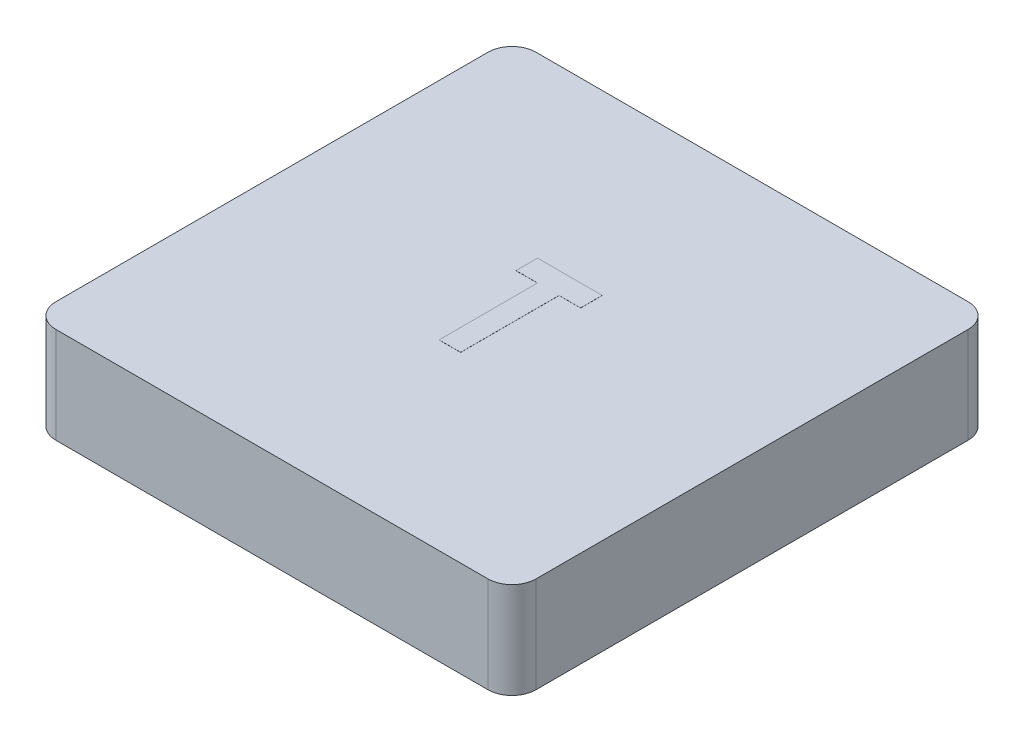
SolidWorks part; units mm, degrees
ref_plane "Front Plane" through (0, 0, 0) normal (0, 0, 1) x (1, 0, 0)
ref_plane "Top Plane" through (0, 0, 0) normal (0, 1, 0) x (1, 0, 0)
ref_plane "Right Plane" through (0, 0, 0) normal (1, 0, 0) x (0, 0, -1)
sketch "Sketch1" plane through (0, 0, 0) normal (0, 1, 0) x (1, 0, 0)
  line L0 (0, 0) -> (12.7, 0)
  line L1 (12.7, 0) -> (12.7, 12.7)
  line L2 (12.7, 12.7) -> (0, 12.7)
  line L3 (0, 12.7) -> (0, 0)
  dimension "D1" = 12.7
  dimension "D2" = 12.7
extrude "Boss-Extrude1" add sketch "Sketch1" along normal blind 2.54
fillet "Fillet1" radius 0.635 4 edges at (0, 1.27, -12.7) (12.7, 1.27, -12.7) (12.7, 1.27, 0) (0, 1.27, 0)
shell "Shell1" thickness 0.635 removed face at (6.35, 0, -6.35)
sketch "Sketch2" plane through (0, 1.905, 0) normal (0, -1, 0) x (-1, 0, 0)
  line L0 (-0.635, 6.35) -> (-12.065, 6.35) construction
  line L1 (-0.635, 12.065) -> (-0.635, 0.635) construction
  line L2 (-12.065, 0.635) -> (-12.065, 12.065) construction
  line L3 (-6.35, 0.635) -> (-6.35, 12.065) construction
  line L4 (-0.635, 0.635) -> (-12.065, 0.635) construction
  line L5 (-12.065, 12.065) -> (-0.635, 12.065) construction
  circle A0 centre (-6.35, 6.35) radius 2.54
  dimension "D1" = 5.08
extrude "Boss-Extrude2" add sketch "Sketch2" along normal up to surface (1.905 mm away) up to face at (6.35, 0, -6.35)
sketch "Sketch3" plane through (0, 2.54, 0) normal (0, 1, 0) x (1, 0, 0)
  line L0 (0, 12.065) -> (0, 0.635) construction
  line L1 (0.635, 0) -> (12.065, 0) construction
  text T0 "<b>T</b>"
  point P1 (0, 0)
  dimension "D1" = 5.334
  dimension "D2" = 4.826
extrude "Boss-Extrude3" add sketch "Sketch3" along normal blind 0.0025
